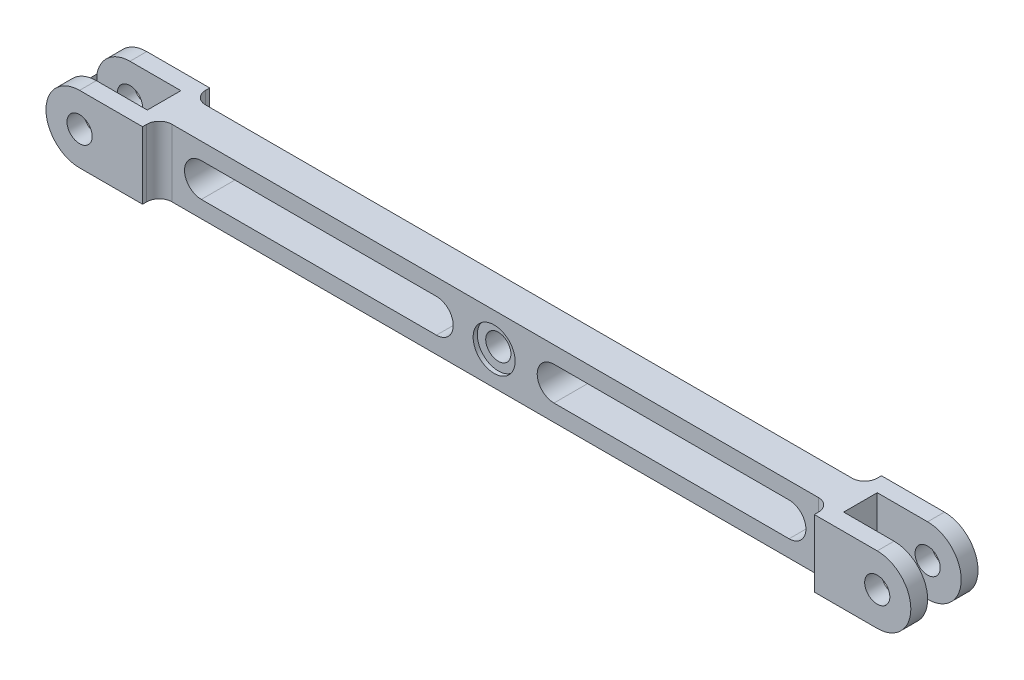
SolidWorks part; units mm, degrees
ref_plane "Front Plane" through (0, 0, 0) normal (0, 0, 1) x (1, 0, 0)
ref_plane "Top Plane" through (0, 0, 0) normal (0, 1, 0) x (1, 0, 0)
ref_plane "Right Plane" through (0, 0, 0) normal (1, 0, 0) x (0, 0, -1)
sketch "Sketch1" plane through (0, 0, 0) normal (0, 0, 1) x (1, 0, 0)
  line L0 (-70, 0) -> (-14, 0) construction
  line L1 (94.9956, 8) -> (-94.9956, 8)
  line L3 (94.9956, -8) -> (-94.9956, -8)
  line L4 (-70, 4) -> (-14, 4)
  line L5 (-70, -4) -> (-14, -4)
  line L6 (14, 0) -> (70, 0) construction
  line L7 (14, 4) -> (70, 4)
  line L8 (14, -4) -> (70, -4)
  circle A0 centre (-0.2585, -0.0201) radius 5
  circle A1 centre (-0.2585, -0.0201) radius 3
  circle A2 centre (-94.9956, 0) radius 3
  circle A3 centre (94.9956, 0) radius 3
  arc A4 (-94.9956, 8) -> (-94.9956, -8) centre (-94.9956, 0) ccw
  arc A5 (94.9956, -8) -> (94.9956, 8) centre (94.9956, 0) ccw
  arc A6 (-70, 4) -> (-70, -4) centre (-70, 0) ccw
  arc A7 (-14, -4) -> (-14, 4) centre (-14, 0) ccw
  arc A8 (14, 4) -> (14, -4) centre (14, 0) ccw
  arc A9 (70, -4) -> (70, 4) centre (70, 0) ccw
  point P0 (0, 0)
  point P1 (-42, 0)
  point P20 (42, 0)
  dimension "D2" = 10
  dimension "D3" = 6
  dimension "D4" = 6
  dimension "D5" = 6
  dimension "D6" = 16
  dimension "D7" = 16
  dimension "D12" = 0
  dimension "D8" = 16
  dimension "D9" = 8
  dimension "D10" = 8
  dimension "D11" = 0
  dimension "D13" = 8
  dimension "D14" = 56
  dimension "D15" = 56
  dimension "D16" = 14
  dimension "D17" = 14
extrude "Boss-Extrude1" add sketch "Sketch1" along normal mid plane 16 contours L3 A5 L1 A4 A9 L8 A8 L7 A7 L5 A6 L4 A0 A2 A3 region at (100.9295, 0, 0)
extrude "Boss-Extrude2" add sketch "Sketch1<4>" along normal mid plane 6 contours A0 A1 region at (-5.1171, -0.0201, 0)
sketch "Sketch1<4>" plane through (0, 0, 0) normal (0, 0, 1) x (1, 0, 0) same geometry as "Sketch1"
sketch "Sketch2" plane through (0, 8, 0) normal (0, 1, 0) x (1, 0, 0)
  line L0 (94.9956, 8) -> (-94.9956, 8) construction
  line L1 (-80, 8) -> (80, 8)
  line L2 (-80, 8) -> (-80, 7)
  line L4 (-77, 4) -> (77, 4)
  line L6 (80, 8) -> (80, 7)
  line L7 (94.9956, -8) -> (-94.9956, -8) construction
  line L8 (80, -8) -> (-80, -8)
  line L9 (80, -8) -> (80, -7)
  line L10 (77, -4) -> (-77, -4)
  line L12 (-80, -8) -> (-80, -7)
  line L14 (102.9956, -8) -> (102.9956, 8) construction
  line L15 (-102.8667, 4) -> (-82.8667, 4)
  line L16 (-102.8667, 4) -> (-102.8667, -4)
  line L17 (-102.8667, -4) -> (-82.8667, -4)
  line L18 (-82.8667, 4) -> (-82.8667, -4)
  line L19 (102.9956, 4) -> (82.9956, 4)
  line L20 (102.9956, 4) -> (102.9956, -4)
  line L21 (102.9956, -4) -> (82.9956, -4)
  line L22 (82.9956, 4) -> (82.9956, -4)
  arc A0 (-80, -7) -> (-77, -4) centre (-77, -7) cw
  arc A1 (80, -7) -> (77, -4) centre (77, -7) ccw
  arc A2 (77, 4) -> (80, 7) centre (77, 7) ccw
  arc A3 (-77, 4) -> (-80, 7) centre (-77, 7) cw
  point P30 (-80, -4)
  point P33 (80, -4)
  point P36 (80, 4)
  point P39 (-80, 4)
  dimension "D12" = 3
  dimension "D1" = 160
  dimension "D2" = 4
  dimension "D3" = 160
  dimension "D4" = 4
  dimension "D5" = 8
  dimension "D6" = 20
  dimension "D7" = 4
  dimension "D8" = 20
  dimension "D9" = 8
  dimension "D10" = 4
  dimension "D11" = 80
  dimension "D13" = 80
extrude "Cut-Extrude2" cut sketch "Sketch2" against normal through all
